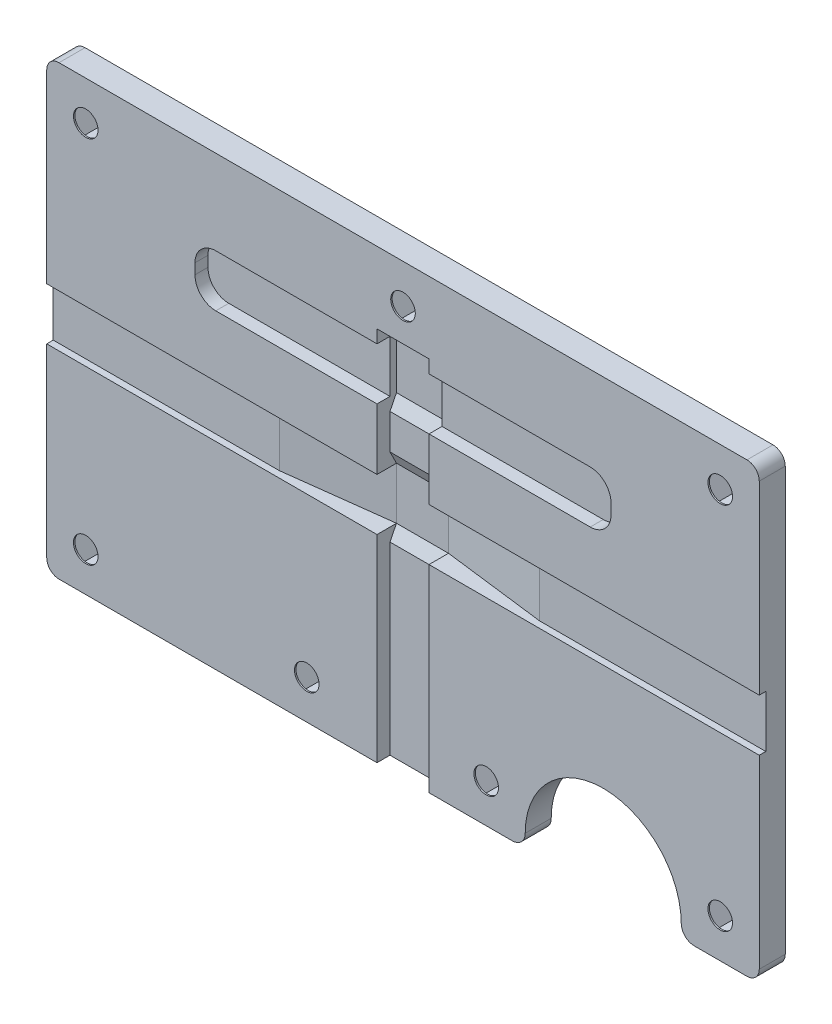
SolidWorks part; units mm, degrees
ref_plane "Front Plane" through (0, 0, 0) normal (0, 0, 1) x (1, 0, 0)
ref_plane "Top Plane" through (0, 0, 0) normal (0, 1, 0) x (1, 0, 0)
ref_plane "Right Plane" through (0, 0, 0) normal (1, 0, 0) x (0, 0, -1)
ref_plane "Plane1" through (0, 0, 1.6) normal (0, 0, 1) x (1, 0, 0)
sketch "Sketch1" plane through (0, 0, 1.6) normal (0, 0, 1) x (1, 0, 0)
  line L0 (-17.6412, 51.7305) -> (-17.6412, 0.1205)
  line L1 (-16.1412, -1.3795) -> (39.1913, -1.3795)
  line L2 (61.4163, -1.3795) -> (67.8538, -1.3795)
  line L3 (69.3538, 0.1205) -> (69.3538, 51.7305)
  line L4 (67.8538, 53.2305) -> (-16.1412, 53.2305)
  line L5 (25.8563, 53.1969) -> (25.8563, 50053.1969) construction
  line L6 (59.8288, 0.6891) -> (59.8288, -49999.3109) construction
  line L7 (-12.8787, 3.383) -> (36.0163, 3.383) construction
  circle A0 centre (-12.8787, 48.468) radius 1.5
  circle A1 centre (-12.8787, 3.383) radius 1.5
  circle A2 centre (64.5913, 3.383) radius 1.5
  circle A3 centre (64.5913, 48.468) radius 1.5
  circle A4 centre (14.1088, 3.383) radius 1.5
  circle A5 centre (36.0163, 3.383) radius 1.5
  circle A6 centre (25.8563, 48.468) radius 1.5
  arc A7 (-17.6412, 0.1205) -> (-16.1412, -1.3795) centre (-16.1412, 0.1205) ccw
  arc A8 (39.1913, -1.3795) -> (40.7788, 0.208) centre (39.1913, 0.208) ccw
  arc A9 (40.7788, 0.208) -> (59.8288, 0.208) centre (50.3038, 0.208) cw
  arc A10 (59.8288, 0.208) -> (61.4163, -1.3795) centre (61.4163, 0.208) ccw
  arc A11 (67.8538, -1.3795) -> (69.3538, 0.1205) centre (67.8538, 0.1205) ccw
  arc A12 (69.3538, 51.7305) -> (67.8538, 53.2305) centre (67.8538, 51.7305) ccw
  arc A13 (-16.1412, 53.2305) -> (-17.6412, 51.7305) centre (-16.1412, 51.7305) ccw
  point P35 (25.8563, 53.2305)
  point P36 (11.5688, 3.383)
  dimension "D1" = 4.7625
  dimension "D2" = 3
  dimension "D4" = 86.995
  dimension "D6" = 4.7625
  dimension "D13" = 1.5875
  dimension "D14" = 9.525
  dimension "D3" = 4.7625
  dimension "D5" = 54.61
  dimension "D7" = 4.7625
  dimension "D8" = 4.7625
  dimension "D9" = 4.7625
  dimension "D10" = 4.7625
  dimension "D11" = 4.7625
  dimension "D12" = 4.7625
  dimension "D15" = 19.05
  dimension "D16" = 4.7625
  dimension "D17" = 4.7625
  dimension "D18" = 3.175
  dimension "D19" = 31.75
extrude "Boss-Extrude1" add sketch "Sketch1" against normal blind 3.175
sketch "Sketch2" plane through (0, 0, 1.6) normal (0, 0, 1) x (1, 0, 0)
  line L0 (-17.6412, 51.7305) -> (-17.6412, 0.1205) construction
  line L1 (-17.6412, 29.1005) -> (69.3538, 29.1005)
  line L2 (-17.6412, 29.1005) -> (-17.6412, 22.7505)
  line L3 (-17.6412, 22.7505) -> (69.3538, 22.7505)
  line L4 (69.3538, 29.1005) -> (69.3538, 22.7505)
  line L5 (69.3538, 51.7305) -> (69.3538, 0.1205) construction
  point P10 (-17.6412, 25.9255)
  dimension "D1" = 6.35
extrude "Cut-Extrude1" cut sketch "Sketch2" against normal blind 0.7937
sketch "Sketch3" plane through (0, 0, 1.6) normal (0, 0, 1) x (1, 0, 0)
  line L0 (-16.1412, -1.3795) -> (67.8538, -1.3795) construction
  line L1 (22.6813, 29.1005) -> (29.0313, 29.1005)
  line L2 (22.6813, 29.1005) -> (22.6813, -1.3795)
  line L3 (22.6813, -1.3795) -> (29.0313, -1.3795)
  line L4 (29.0313, 29.1005) -> (29.0313, -1.3795)
  line L5 (69.3538, 29.1005) -> (-17.6412, 29.1005) construction
  point P8 (25.8563, -1.3795)
  dimension "D1" = 6.35
extrude "Cut-Extrude2" cut sketch "Sketch3" against normal blind 1.5875
sketch "Sketch4" plane through (0, 0, 1.6) normal (0, 0, 1) x (1, 0, 0)
  line L0 (29.0313, 29.1005) -> (22.6813, 29.1005) construction
  line L1 (22.6813, 44.4992) -> (29.0313, 44.4992)
  line L2 (22.6813, 44.4992) -> (22.6813, 29.1005)
  line L3 (22.6813, 29.1005) -> (29.0313, 29.1005)
  line L4 (29.0313, 44.4992) -> (29.0313, 29.1005)
  line L6 (25.8563, 44.4992) -> (25.8563, -49955.5008) construction
  circle A0 centre (25.8563, 48.468) radius 1.5 construction
  point P6 (25.8563, 29.1005)
  point P7 (25.8563, 29.1005)
  point P17 (25.8563, 44.4992)
  dimension "D1" = 3.9688
extrude "Cut-Extrude3" cut sketch "Sketch4" against normal blind 1.5875
sketch "Sketch6" plane through (0, 0, 0.0125) normal (0, 0, 1) x (1, 0, 0)
  line L0 (25.8563, 44.1805) -> (25.8563, -49955.8195) construction
  line L1 (22.6813, 42.9117) -> (29.0313, 42.9117)
  line L2 (22.6813, 42.9117) -> (22.6813, 36.5617)
  line L3 (22.6813, 36.5617) -> (29.0313, 36.5617)
  line L4 (29.0313, 42.9117) -> (29.0313, 36.5617)
  line L5 (29.0313, 44.4992) -> (22.6813, 44.4992) construction
  line L6 (29.0313, -1.3795) -> (29.0313, 44.4992) construction
  line L7 (29.0313, 44.4992) -> (22.6813, 44.4992) construction
  point P8 (25.8563, 44.4992)
  point P9 (25.8563, 42.9117)
  dimension "D1" = 1.5875
  dimension "D2" = 6.35
extrude "Cut-Extrude4" cut sketch "Sketch6" against normal blind 0.7937
chamfer "Chamfer2" distance 1.5875 distance2 0.7937 2 edges at (25.8563, 36.5617, 0.0125) (25.8563, 42.9117, 0.0125) first distance on face at (25.8563, 17.5911, 0.0125) first distance on face at (25.8563, 43.7055, 0.0125)
sketch "Sketch7" plane through (0, 0, 1.6) normal (0, 0, 1) x (1, 0, 0)
  line L0 (29.0313, 42.9117) -> (22.6813, 42.9117) construction
  line L1 (48.7163, 42.9117) -> (2.9963, 42.9117)
  line L2 (51.2563, 40.3717) -> (51.2563, 39.1017)
  line L3 (48.7163, 36.5617) -> (2.9963, 36.5617)
  line L4 (0.4563, 40.3717) -> (0.4563, 39.1017)
  line L7 (22.6813, 36.5617) -> (29.0313, 36.5617) construction
  arc A0 (51.2563, 40.3717) -> (48.7163, 42.9117) centre (48.7163, 40.3717) ccw
  arc A1 (48.7163, 36.5617) -> (51.2563, 39.1017) centre (48.7163, 39.1017) ccw
  arc A2 (0.4563, 39.1017) -> (2.9963, 36.5617) centre (2.9963, 39.1017) ccw
  arc A3 (0.4563, 40.3717) -> (2.9963, 42.9117) centre (2.9963, 40.3717) cw
  point P8 (25.8563, 42.9117)
  point P9 (25.8563, 42.9117)
  point P14 (51.2563, 36.5617)
  point P17 (0.4563, 36.5617)
  dimension "D2" = 2.54
  dimension "D1" = 50.8
extrude "Cut-Extrude5" cut sketch "Sketch7" against normal blind 1.5875
sketch "Sketch9" plane through (0, 0, -1.575) normal (0, 0, -1) x (-1, 0, 0)
  line L1 (-22.6231, 48.4534) -> (-24.2271, 51.2607)
  line L2 (-24.2271, 51.2607) -> (-27.4602, 51.2752)
  line L3 (-27.4602, 51.2752) -> (-29.0894, 48.4825)
  line L4 (-29.0894, 48.4825) -> (-27.4854, 45.6753)
  line L5 (-27.4854, 45.6753) -> (-24.2523, 45.6607)
  line L6 (-24.2523, 45.6607) -> (-22.6231, 48.4534)
  line L7 (-10.8756, 3.3755) -> (-12.4857, 6.1792)
  line L8 (-12.4857, 6.1792) -> (-15.7188, 6.1867)
  line L9 (-15.7188, 6.1867) -> (-17.3419, 3.3905)
  line L10 (-17.3419, 3.3905) -> (-15.7319, 0.5868)
  line L11 (-15.7319, 0.5868) -> (-12.4987, 0.5792)
  line L12 (-12.4987, 0.5792) -> (-10.8756, 3.3755)
  line L13 (16.1119, 3.3696) -> (14.5069, 6.1763)
  line L14 (14.5069, 6.1763) -> (11.2737, 6.1897)
  line L15 (11.2737, 6.1897) -> (9.6456, 3.3964)
  line L16 (9.6456, 3.3964) -> (11.2506, 0.5897)
  line L17 (11.2506, 0.5897) -> (14.4837, 0.5763)
  line L18 (14.4837, 0.5763) -> (16.1119, 3.3696)
  line L19 (16.1118, 48.4454) -> (14.5148, 51.2566)
  line L20 (14.5148, 51.2566) -> (11.2817, 51.2792)
  line L21 (11.2817, 51.2792) -> (9.6456, 48.4906)
  line L22 (9.6456, 48.4906) -> (11.2426, 45.6793)
  line L23 (11.2426, 45.6793) -> (14.4757, 45.6568)
  line L24 (14.4757, 45.6568) -> (16.1118, 48.4454)
  line L25 (-61.3581, 48.4682) -> (-62.9749, 51.2681)
  line L26 (-62.9749, 51.2681) -> (-66.208, 51.2679)
  line L27 (-66.208, 51.2679) -> (-67.8244, 48.4678)
  line L28 (-67.8244, 48.4678) -> (-66.2077, 45.6679)
  line L29 (-66.2077, 45.6679) -> (-62.9745, 45.6681)
  line L30 (-62.9745, 45.6681) -> (-61.3581, 48.4682)
  line L31 (-61.3581, 3.383) -> (-62.9747, 6.183)
  line L32 (-62.9747, 6.183) -> (-66.2079, 6.183)
  line L33 (-66.2079, 6.183) -> (-67.8244, 3.383)
  line L34 (-67.8244, 3.383) -> (-66.2079, 0.583)
  line L35 (-66.2079, 0.583) -> (-62.9747, 0.583)
  line L36 (-62.9747, 0.583) -> (-61.3581, 3.383)
  line L37 (-32.7843, 3.2953) -> (-34.3243, 6.1381)
  line L38 (-34.3243, 6.1381) -> (-37.5563, 6.2258)
  line L39 (-37.5563, 6.2258) -> (-39.2482, 3.4707)
  line L40 (-39.2482, 3.4707) -> (-37.7082, 0.6279)
  line L41 (-37.7082, 0.6279) -> (-34.4762, 0.5402)
  line L42 (-34.4762, 0.5402) -> (-32.7843, 3.2953)
  circle A0 centre (-25.8563, 48.468) radius 2.8 construction
  circle A1 centre (-14.1088, 3.383) radius 2.8 construction
  circle A2 centre (12.8787, 3.383) radius 2.8 construction
  circle A3 centre (12.8787, 48.468) radius 2.8 construction
  circle A4 centre (-64.5913, 48.468) radius 2.8 construction
  circle A5 centre (-64.5913, 48.468) radius 1.5 construction
  circle A6 centre (-25.8563, 48.468) radius 1.5 construction
  circle A7 centre (12.8787, 48.468) radius 1.5 construction
  circle A8 centre (12.8787, 3.383) radius 1.5 construction
  circle A9 centre (-14.1088, 3.383) radius 1.5 construction
  circle A10 centre (-64.5913, 3.383) radius 2.8 construction
  circle A11 centre (-36.0163, 3.383) radius 2.8 construction
  circle A12 centre (-36.0163, 3.383) radius 1.5 construction
  circle A13 centre (-64.5913, 3.383) radius 1.5 construction
  dimension "D1" = 5.6
extrude "Cut-Extrude6" cut sketch "Sketch9" against normal blind 3
sketch "Sketch11" plane through (0, 0, 0.0125) normal (0, 0, 1) x (1, 0, 0)
  line L1 (22.6813, 29.1005) -> (29.0313, 29.1005)
  line L2 (22.6813, 29.1005) -> (22.6813, 22.7505)
  line L3 (22.6813, 22.7505) -> (29.0313, 22.7505)
  line L4 (29.0313, 29.1005) -> (29.0313, 22.7505)
  line L6 (29.0313, -1.3795) -> (29.0313, 34.9742) construction
  line L7 (22.6813, 34.9742) -> (22.6813, -1.3795) construction
  line L8 (20.5291, 22.7505) -> (50020.5291, 22.7505) construction
  line L11 (20.4537, 29.1005) -> (50020.4537, 29.1005) construction
  line L13 (29.0313, 22.7505) -> (69.3538, 22.7505) construction
  line L14 (69.3538, 29.1005) -> (29.0313, 29.1005) construction
extrude "Cut-Extrude8" cut sketch "Sketch11" against normal blind 0.7937
chamfer "Chamfer3" distance 12.7 distance2 1.5875 2 edges at (22.6813, 25.9255, 0.8063) (29.0313, 25.9255, 0.8063) first distance on face at (2.52, 25.9255, 0.8063) first distance on face at (49.1925, 25.9255, 0.8063)
chamfer "Chamfer4" distance 1.5875 distance2 0.7937 2 edges at (25.8563, 22.7505, 0.0125) (25.8563, 29.1005, 0.0125) first distance on face at (25.8563, 10.6855, 0.0125) first distance on face at (25.8563, 32.0374, 0.0125)
